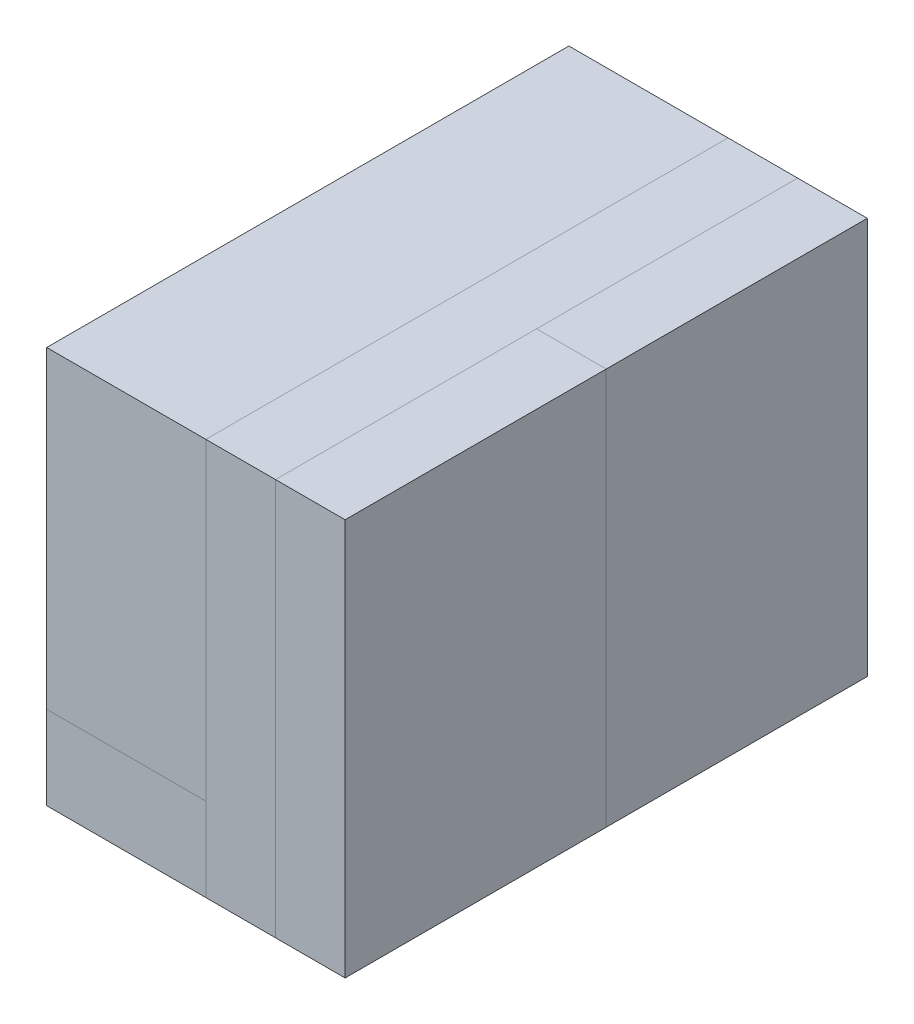
SolidWorks part; units mm, degrees
ref_plane "前视基准面" through (0, 0, 0) normal (0, 0, 1) x (1, 0, 0)
ref_plane "上视基准面" through (0, 0, 0) normal (0, 1, 0) x (1, 0, 0)
ref_plane "右视基准面" through (0, 0, 0) normal (1, 0, 0) x (0, 0, -1)
sketch "草图1" plane through (0, 0, 0) normal (0, 1, 0) x (1, 0, 0)
  line L1 (0, 0) -> (228.6, 0)
  line L2 (0, 0) -> (0, 750)
  line L3 (0, 750) -> (228.6, 750)
  line L4 (228.6, 0) -> (228.6, 750)
  dimension "D1" = 750
  dimension "D2" = 228.6
extrude "墙体支撑底座" add sketch "草图1" along normal blind 120
sketch "草图3" plane through (0, 120, 0) normal (0, 1, 0) x (1, 0, 0)
  line L1 (0, 0) -> (228.6, 0)
  line L2 (0, 0) -> (0, 750)
  line L3 (0, 750) -> (228.6, 750)
  line L4 (228.6, 0) -> (228.6, 750)
extrude "18寸墙体" add sketch "草图3" along normal blind 450 separate body
sketch "草图5" plane through (228.6, 0, 0) normal (1, 0, 0) x (0, 0, -1)
  line L1 (0, 570) -> (750, 570)
  line L2 (0, 570) -> (0, 0)
  line L3 (0, 0) -> (750, 0)
  line L4 (750, 570) -> (750, 0)
extrude "2x液晶挂壁" add sketch "草图5" along normal blind 100 separate body
sketch "草图6" plane through (328.6, 0, 0) normal (1, 0, 0) x (0, 0, -1)
  line L0 (0, 0) -> (750, 0) construction
  line L1 (0, 570) -> (375, 570)
  line L2 (0, 570) -> (0, 0)
  line L3 (0, 0) -> (375, 0)
  line L4 (375, 570) -> (375, 0)
extrude "1x液晶显示器" add sketch "草图6" along normal blind 100 separate body
sketch "草图7" plane through (328.6, 0, 0) normal (1, 0, 0) x (0, 0, -1)
  line L1 (375, 570) -> (750, 570)
  line L2 (375, 570) -> (375, 0)
  line L3 (375, 0) -> (750, 0)
  line L4 (750, 570) -> (750, 0)
extrude "工具存放区" add sketch "草图7" along normal blind 100 separate body
